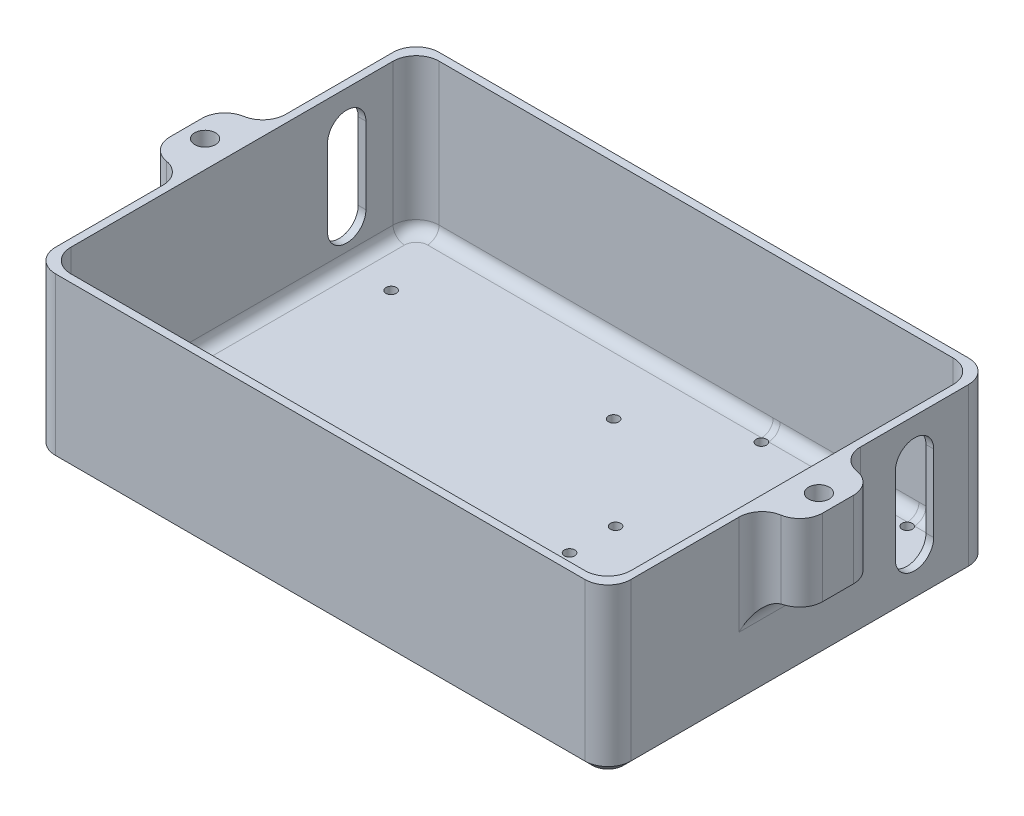
SolidWorks part; units mm, degrees
ref_plane "Front Plane" through (0, 0, 0) normal (0, 0, 1) x (1, 0, 0)
ref_plane "Top Plane" through (0, 0, 0) normal (0, 1, 0) x (1, 0, 0)
ref_plane "Right Plane" through (0, 0, 0) normal (1, 0, 0) x (0, 0, -1)
sketch "Sketch1" plane through (0, 0, 0) normal (0, 1, 0) x (1, 0, 0)
  line L0 (0, 0) -> (-32.5, 0) construction
  line L1 (-75, -50) -> (75, -50)
  line L2 (-75, -50) -> (-75, 50)
  line L3 (-75, 50) -> (75, 50)
  line L4 (75, -50) -> (75, 50)
  line L5 (-75, -50) -> (75, 50) construction
  line L6 (-75, 50) -> (75, -50) construction
  line L7 (0, 0) -> (40, 0) construction
  line L8 (-61.5, -30) -> (-3.5, -30) construction
  line L9 (-61.5, -30) -> (-61.5, 30) construction
  line L10 (-61.5, 30) -> (-3.5, 30) construction
  line L11 (-3.5, -30) -> (-3.5, 30) construction
  line L12 (-61.5, -30) -> (-3.5, 30) construction
  line L13 (-61.5, 30) -> (-3.5, -30) construction
  line L14 (40, 0) -> (40, 25) construction
  line L15 (21, -6) -> (59, -44) construction
  line L16 (21, 44) -> (59, 44) construction
  line L17 (21, 44) -> (21, 6) construction
  line L18 (21, 6) -> (59, 6) construction
  line L19 (59, 44) -> (59, 6) construction
  line L20 (21, 44) -> (59, 6) construction
  line L21 (21, 6) -> (59, 44) construction
  line L22 (21, -44) -> (59, -6) construction
  line L23 (59, -44) -> (59, -6) construction
  line L24 (21, -6) -> (59, -6) construction
  line L25 (21, -44) -> (21, -6) construction
  line L26 (21, -44) -> (59, -44) construction
  circle A0 centre (-61.5, 30) radius 1.35
  circle A1 centre (-3.5, 30) radius 1.35
  circle A2 centre (-61.5, -30) radius 1.35
  circle A3 centre (-3.5, -30) radius 1.35
  circle A4 centre (21, 44) radius 1.35
  circle A5 centre (59, 44) radius 1.35
  circle A6 centre (21, 6) radius 1.35
  circle A7 centre (59, 6) radius 1.35
  circle A8 centre (59, -6) radius 1.35
  circle A9 centre (21, -6) radius 1.35
  circle A10 centre (59, -44) radius 1.35
  circle A11 centre (21, -44) radius 1.35
  point P0 (0, 0)
  point P12 (-32.5, -30)
  dimension "D5" = 40
  dimension "D1" = 150
  dimension "D2" = 100
  dimension "D3" = 58
  dimension "D4" = 60
  dimension "D6" = 25
  dimension "D7" = 38
  dimension "D8" = 38
extrude "Boss-Extrude1" add sketch "Sketch1" along normal blind 3
sketch "Sketch2" plane through (0, 3, 0) normal (0, 1, 0) x (1, 0, 0)
  line L0 (-73, 48) -> (73, 48)
  line L1 (-75, 50) -> (75, 50)
  line L2 (-75, 50) -> (-75, -50)
  line L3 (-75, -50) -> (75, -50)
  line L4 (75, 50) -> (75, -50)
  line L5 (73, 48) -> (73, -48)
  line L6 (-73, -48) -> (73, -48)
  line L7 (-73, 48) -> (-73, -48)
  dimension "D1" = 2
extrude "Boss-Extrude2" add sketch "Sketch2" along normal blind 40
fillet "Fillet1" radius 6 4 edges at (-73, 23, 48) (73, 23, 48) (73, 23, -48) (-73, 23, -48)
sketch "Sketch4" plane through (0, 43, 0) normal (0, 1, 0) x (1, 0, 0)
  line L0 (75, -50) -> (75, 0) construction
  line L1 (0, 0) -> (0, -50) construction
  line L2 (75, -50) -> (75, 50) construction
  line L3 (75, 0) -> (80, 0) construction
  line L4 (-75, -50) -> (75, -50) construction
  line L5 (85, -10) -> (75, -10)
  line L6 (85, -10) -> (85, 10)
  line L7 (85, 10) -> (75, 10)
  line L8 (75, -10) -> (75, 10)
  line L9 (85, -10) -> (75, 10) construction
  line L10 (85, 10) -> (75, -10) construction
  line L11 (-85, 10) -> (-75, -10) construction
  line L12 (-85, -10) -> (-75, 10) construction
  line L13 (-75, 0) -> (-80, 0) construction
  line L14 (-75, -10) -> (-75, 10)
  line L15 (-85, 10) -> (-75, 10)
  line L16 (-85, -10) -> (-85, 10)
  line L17 (-85, -10) -> (-75, -10)
  circle A0 centre (80, 0) radius 2.7
  circle A1 centre (-80, 0) radius 2.7
  dimension "D2" = 5
  dimension "D1" = 20
  dimension "D3" = 10
extrude "Boss-Extrude3" add sketch "Sketch4" against normal blind 20
sketch "Sketch5" plane through (0, 23, 0) normal (0, -1, 0) x (1, 0, 0)
  circle A0 centre (-80, 0) radius 4.5
  circle A1 centre (80, 0) radius 4.5
  dimension "D1" = 9
  dimension "D2" = 9
extrude "Cut-Extrude1" cut sketch "Sketch5" against normal blind 15
fillet "Fillet2" radius 6 3 edges at (-75, 33, -10) (-75, 33, 10) (-75, 23, 0)
fillet "Fillet5" radius 6 1 edges at (-85, 33, 10)
fillet "Fillet6" radius 6 1 edges at (-85, 33, -10)
fillet "Fillet7" radius 6 1 edges at (85, 33, 10)
fillet "Fillet8" radius 6 1 edges at (85, 33, -10)
fillet "Fillet9" radius 6 3 edges at (75, 33, -10) (75, 23, 0) (75, 33, 10)
fillet "Fillet3" radius 6 4 edges at (75, 21.5, -50) (75, 21.5, 50) (-75, 21.5, 50) (-75, 21.5, -50)
fillet "Fillet4" radius 3 8 edges at (71.2426, 3, -46.2426) (73, 3, 0) (71.2426, 3, 46.2426) (0, 3, 48) (-71.2426, 3, 46.2426) (-73, 3, 0) (-71.2426, 3, -46.2426) (0, 3, -48)
chamfer "Chamfer1" distance 2 angle 45 8 edges at (0, 0, 50) (73.2426, 0, 48.2426) (-73.2426, 0, 48.2426) (75, 0, 0) (-75, 0, 0) (73.2426, 0, -48.2426) (-73.2426, 0, -48.2426) (0, 0, -50)
sketch "Sketch7" plane through (75, 0, 0) normal (1, 0, 0) x (0, 0, -1)
  line L0 (44, 43) -> (29.9161, 43) construction
  line L1 (15.8322, 43) -> (44, 43) construction
  line L2 (29.9161, 43) -> (29.9161, 23) construction
  line L3 (29.9161, 13) -> (29.9161, 33) construction
  line L4 (24.9161, 13) -> (24.9161, 33)
  line L5 (34.9161, 13) -> (34.9161, 33)
  arc A0 (24.9161, 13) -> (34.9161, 13) centre (29.9161, 13) ccw
  arc A1 (34.9161, 33) -> (24.9161, 33) centre (29.9161, 33) ccw
  point P8 (29.9161, 23)
extrude "Cut-Extrude2" cut sketch "Sketch7" against normal blind 167
